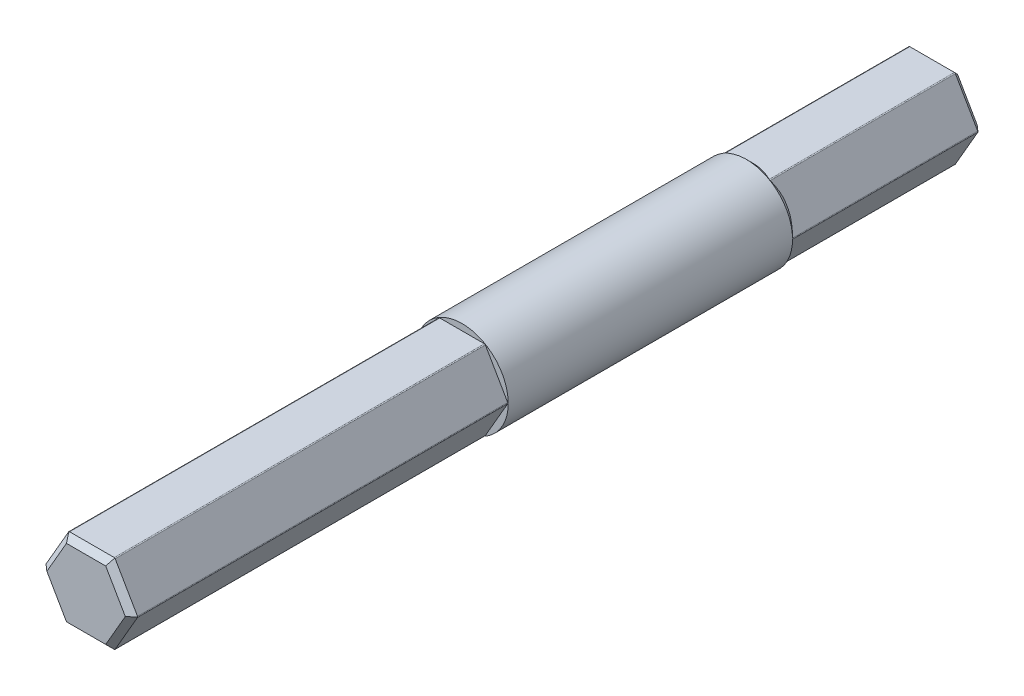
SolidWorks part; units mm, degrees
material "PETG"
ref_plane "Front Plane" through (0, 0, 0) normal (0, 0, 1) x (1, 0, 0)
ref_plane "Top Plane" through (0, 0, 0) normal (0, 1, 0) x (1, 0, 0)
ref_plane "Right Plane" through (0, 0, 0) normal (1, 0, 0) x (0, 0, -1)
sketch "Sketch1" plane through (0, 0, 0) normal (0, 0, 1) x (1, 0, 0)
  circle A0 centre (0, 0) radius 3.975
  dimension "Shaft Dia" = 7.95
extrude "Boss-Extrude1" add sketch "Sketch1" along normal blind 25
sketch "Sketch2" plane through (0, 0, 25) normal (0, 0, 1) x (1, 0, 0)
  line L1 (4, 0) -> (2, 3.4641) construction
  line L2 (2, 3.4641) -> (-2, 3.4641) construction
  line L3 (-2, 3.4641) -> (-4, 0) construction
  line L4 (-4, 0) -> (-2, -3.4641) construction
  line L5 (-2, -3.4641) -> (2, -3.4641) construction
  line L6 (2, -3.4641) -> (4, 0) construction
  line L7 (3.9567, 0) -> (1.9783, 3.4266)
  line L8 (1.9783, 3.4266) -> (-1.9783, 3.4266)
  line L9 (-1.9783, 3.4266) -> (-3.9567, 0)
  line L10 (-3.9567, 0) -> (-1.9783, -3.4266)
  line L11 (-1.9783, -3.4266) -> (1.9783, -3.4266)
  line L12 (1.9783, -3.4266) -> (3.9567, 0)
  circle A0 centre (0, 0) radius 3.4641 construction
  circle A1 centre (0, 0) radius 3.4266 construction
  dimension "Hex Circumscribed Nominal Dia" = 8
  dimension "Hex Flat To Flat Offset" = 0.0375
extrude "Boss-Extrude2" add sketch "Sketch2" along normal blind 32.4
sketch "Sketch3" plane through (0, 0, 0) normal (0, 0, -1) x (-1, 0, 0)
  line L0 (-1.9783, 3.4266) -> (1.9783, 3.4266) construction
  line L13 (3.9567, 0) -> (1.9783, 3.4266)
  line L14 (1.9783, 3.4266) -> (-1.9783, 3.4266)
  line L15 (-1.9783, 3.4266) -> (-3.9567, 0)
  line L16 (-3.9567, 0) -> (-1.9783, -3.4266)
  line L17 (-1.9783, -3.4266) -> (1.9783, -3.4266)
  line L18 (1.9783, -3.4266) -> (3.9567, 0)
  circle A1 centre (0, 0) radius 3.4266 construction
extrude "Boss-Extrude3" add sketch "Sketch3" along normal blind 16
chamfer "Chamfer1" distance 0.5 angle 45 12 edges at (0, -3.4266, 57.4) (-2.9675, -1.7133, 57.4) (-2.9675, 1.7133, 57.4) (0, 3.4266, 57.4) (2.9675, 1.7133, 57.4) (2.9675, -1.7133, 57.4) (0, -3.4266, -16) (2.9675, -1.7133, -16) (2.9675, 1.7133, -16) (0, 3.4266, -16) (-2.9675, 1.7133, -16) (-2.9675, -1.7133, -16)
fillet "Fillet1" radius 0.1 12 edges at (-1.9783, 3.4266, -7.75) (-3.9567, 0, -7.75) (1.9783, 3.4266, -7.75) (3.9567, 0, -7.75) (1.9783, -3.4266, -7.75) (-1.9783, -3.4266, -7.75) (1.9783, -3.4266, 40.95) (-1.9783, -3.4266, 40.95) (-3.9567, 0, 40.95) (-1.9783, 3.4266, 40.95) (3.9567, 0, 40.95) (1.9783, 3.4266, 40.95)
chamfer "Chamfer2" distance 0.5 angle 45 1 edges at (3.975, 0, 0)
equation "\"tol_dia_id_intfc\" = 0.0500mm ' For hole diameters - Interference fit"
equation "\"tol_dia_id_slip\"  = 0.0750mm ' For hole diameters - Slip fit"
equation "\"tol_dia_id_clear\" = 0.1000mm ' For hole diameters - Clearance fit"
equation "\"tol_dia_od_intfc\" = 0.0500mm ' For shaft diameters - Interference fit"
equation "\"tol_dia_od_slip\"  = 0.0750mm ' For shaft diameters - Slip fit"
equation "\"tol_dia_od_clear\" = 0.1000mm ' For shaft diameters - Clearance fit"
equation "\"tol_general_intfc\"= 0.0250mm ' For general parts (Horiz) - Interference fit"
equation "\"tol_general_slip\" = 0.0375mm ' For general parts (Horiz) - Slip fit"
equation "\"tol_general_clear\"= 0.0500mm ' For general parts (Horiz) - Clearance fit"
equation "\"tol_layer_intfc\"  = 0.0250mm ' For all parts (Vert) - Interference fit"
equation "\"tol_layer_slip\"   = 0.0375mm ' For all parts (Vert) - Slip fit"
equation "\"tol_layer_clear\"  = 0.0500mm ' For all parts (Vert) - Clearance fit"
equation "\"tol_corner_rad\"   = 0.100mm ' For corners that fit into other parts"
equation "\"Shaft Dia@Sketch1\" = \"nominal_dia\" - \"tol_dia_od_intfc\""
equation "\"nominal_dia\"= 8.00mm"
equation "\"Hex Circumscribed Nominal Dia@Sketch2\" = \"nominal_dia\""
equation "\"Hex Flat To Flat Offset@Sketch2\"=\"tol_general_slip\""
equation "\"D1@Fillet1\"=\"tol_corner_rad\""
equation "\"D1@Boss-Extrude2\"=32.50mm-\"tol_layer_clear\"*2"
